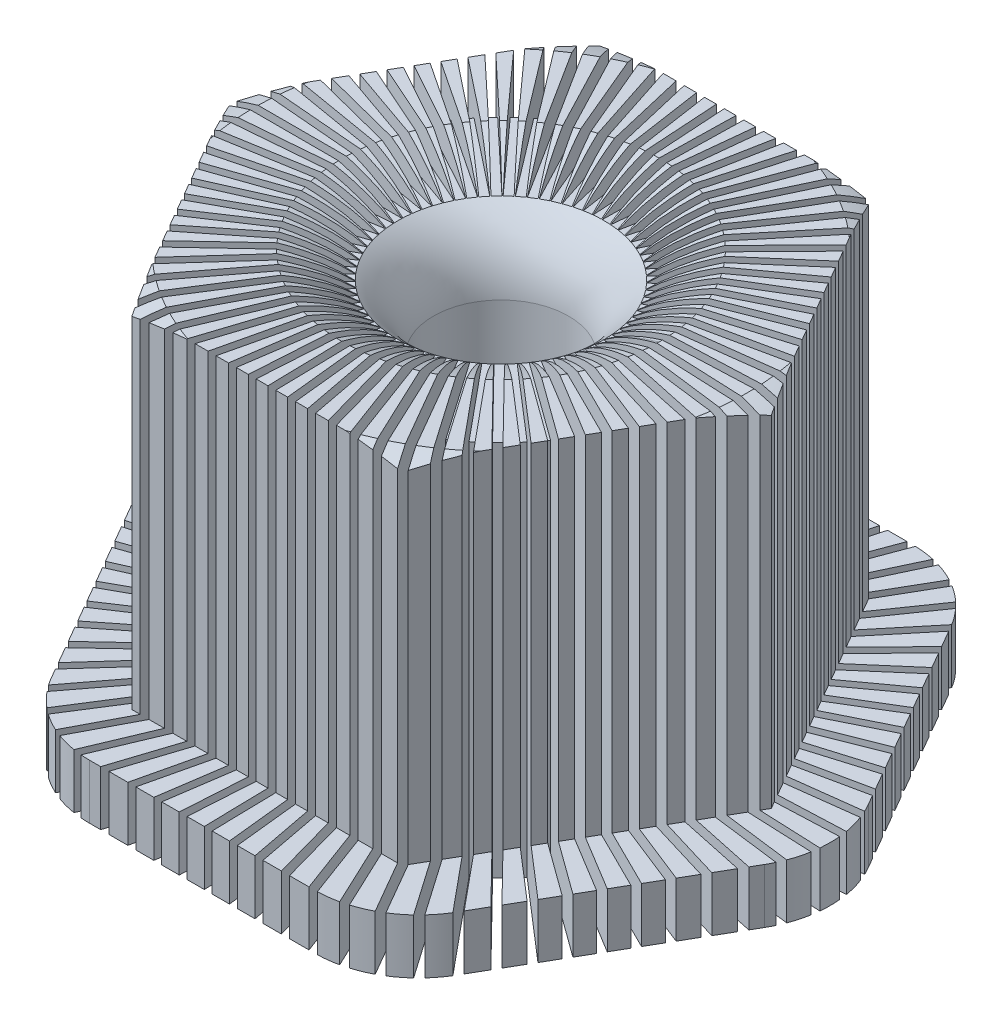
SolidWorks part; units mm, degrees
ref_plane "Front Plane" through (0, 0, 0) normal (0, 0, 1) x (1, 0, 0)
ref_plane "Top Plane" through (0, 0, 0) normal (0, 1, 0) x (1, 0, 0)
ref_plane "Right Plane" through (0, 0, 0) normal (1, 0, 0) x (0, 0, -1)
sketch "Sketch1" plane through (0, 0, 0) normal (0, 1, 0) x (1, 0, 0)
  line L1 (60.6218, 10) -> (38.9711, 47.5)
  line L2 (21.6506, 57.5) -> (-21.6506, 57.5)
  line L3 (-38.9711, 47.5) -> (-60.6218, 10)
  line L4 (-60.6218, -10) -> (-38.9711, -47.5)
  line L5 (-21.6506, -57.5) -> (21.6506, -57.5)
  line L6 (38.9711, -47.5) -> (60.6218, -10)
  circle A0 centre (0, 0) radius 57.5 construction
  arc A1 (-21.6506, -57.5) -> (-38.9711, -47.5) centre (-21.6506, -37.5) cw
  arc A2 (21.6506, -57.5) -> (38.9711, -47.5) centre (21.6506, -37.5) ccw
  arc A3 (60.6218, -10) -> (60.6218, 10) centre (43.3013, 0) ccw
  arc A4 (38.9711, 47.5) -> (21.6506, 57.5) centre (21.6506, 37.5) ccw
  arc A5 (-21.6506, 57.5) -> (-38.9711, 47.5) centre (-21.6506, 37.5) ccw
  arc A6 (-60.6218, -10) -> (-60.6218, 10) centre (-43.3013, 0) cw
  dimension "D1" = 115
  dimension "D2" = 20
extrude "Boss-Extrude2" add sketch "Sketch1" along normal blind 77.5
sketch "Sketch6" plane through (0, 77.5, 0) normal (0, 1, 0) x (1, 0, 0)
  circle A0 centre (0, 0) radius 13
extrude "Cut-Extrude1" cut sketch "Sketch6" against normal up to surface (77.5 mm away) up to face at (0, 0, 0)
sketch "Sketch7" plane through (0, 0, 0) normal (0, 0, 1) x (1, 0, 0)
  line L0 (0, 77.5) -> (0, 0) construction
  line L1 (-21.6506, 77.5) -> (21.6506, 77.5) construction
  line L2 (0, 77.5) -> (13, 77.5) construction
  line L3 (13, 77.5) -> (13, 60)
  line L4 (13, 77.5) -> (30.5, 77.5)
  line L5 (38.9711, 77.5) -> (21.6506, 77.5) construction
  line L6 (13, 0) -> (63.3013, 0) construction
  line L7 (38.9711, 0) -> (38.9711, 77.5) construction
  line L8 (64.9423, 77.5) -> (47.4423, 77.5)
  line L9 (64.9423, 77.5) -> (64.9423, 60)
  line L10 (13, 77.5) -> (-13, 77.5) construction
  line L11 (13, 77.5) -> (18.5176, 71.4317) construction
  spline S0 degree 2 poles (13, 60) (14.0037, 72.8919) (30.5, 77.5) knots 0 0 0 1 1 1
  spline S1 degree 2 poles (64.9423, 60) (63.9386, 72.8919) (47.4423, 77.5) knots 0 0 0 1 1 1
  dimension "D1" = 13
  dimension "D2" = 17.5
  dimension "D3" = 17.5
  dimension "D4" = 8.2017
revolve "Cut-Revolve1" cut sketch "Sketch7" angle 360 about L0
ref_plane "Plane1" through (0, 38.75, 0) normal (0, 1, 0) x (1, 0, 0)
sketch "Sketch8" plane through (0, 0, 0) normal (0, 0, 1) x (1, 0, 0)
  line L0 (-63.3013, 77.5) -> (-63.3013, 0)
  line L1 (-13.3013, 5) -> (-38.3013, 5) construction
  line L2 (-38.3013, 5) -> (-38.3013, 0)
  line L3 (-63.3013, 0) -> (-38.3013, 0)
  line L4 (-13.3013, 0) -> (-13.3013, 5) construction
  line L5 (-38.3013, 5) -> (-38.3013, 72.5)
  line L6 (63.25, 38.75) -> (-63.25, 38.75) construction
  line L7 (-63.3013, 38.75) -> (-38.3013, 38.75) construction
  line L8 (-13.3013, 77.5) -> (-13.3013, 72.5)
  line L9 (-63.3013, 77.5) -> (-13.3013, 77.5)
  line L10 (-13.3013, 72.5) -> (-38.3013, 72.5)
  line L11 (-38.3013, 0) -> (-13.3013, 0) construction
  point P3 (-66.188, 24)
  dimension "D1" = 50
  dimension "D2" = 50
  dimension "D3" = 5
  dimension "D4" = 25
extrude "Cut-Extrude2" cut sketch "Sketch8" against normal blind 0.75 and the other way blind 0.75
pattern_circular "CirPattern1" count 75 over 360 about axis through (0, -36.7696, 0) along (0, 1, 0) of "Cut-Extrude2"
sketch "Sketch9" plane through (0, 77.5, 0) normal (0, 1, 0) x (1, 0, 0)
  line L1 (51.9615, 0) -> (25.9808, 45)
  line L2 (25.9808, 45) -> (-25.9808, 45)
  line L3 (-25.9808, 45) -> (-51.9615, 0)
  line L4 (-51.9615, 0) -> (-25.9808, -45)
  line L5 (-25.9808, -45) -> (25.9808, -45)
  line L6 (25.9808, -45) -> (51.9615, 0)
  circle A0 centre (0, 0) radius 45 construction
  dimension "D1" = 90
extrude "Cut-Extrude3" cut sketch "Sketch9" against normal blind 67 flip side to cut
